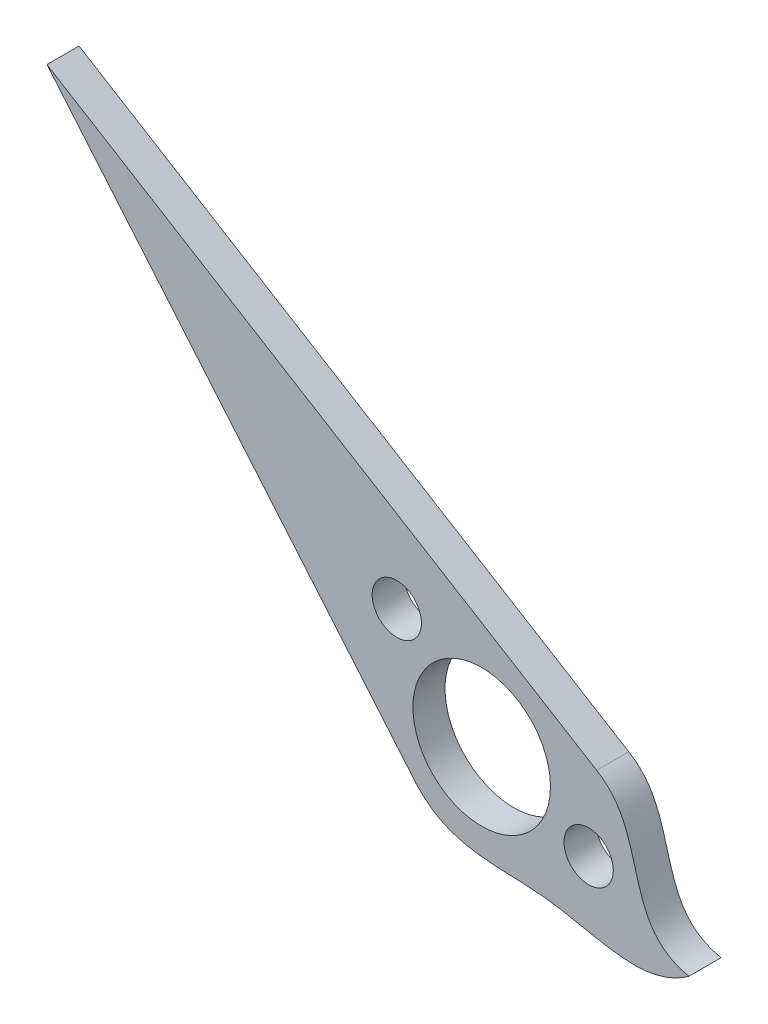
SolidWorks part; units mm, degrees
material "Titanium Ti-5Al-2.5Sn"
ref_plane "Front Plane" through (0, 0, 0) normal (0, 0, 1) x (1, 0, 0)
ref_plane "Top Plane" through (0, 0, 0) normal (0, 1, 0) x (1, 0, 0)
ref_plane "Right Plane" through (0, 0, 0) normal (1, 0, 0) x (0, 0, -1)
sketch "Sketch1" plane through (0, 0, 0) normal (0, 0, 1) x (1, 0, 0)
  line L0 (-5.6865, -5.6666) -> (-37.9242, 32.5846)
  line L1 (-37.9242, 32.5846) -> (10.0269, 3.2434)
  circle A1 centre (0, 0) radius 6
  circle A4 centre (-7.4069, 6.7184) radius 2.15
  circle A5 centre (9.3292, -3.6008) radius 2.15
  spline S0 degree 3 poles (10.0269, 3.2434) (14.6942, 0.5102) (12.1069, -7.0713) (18.0793, -8.2869) knots 0 0 0 0 1 1 1 1
  spline S1 degree 3 poles (-5.6865, -5.6666) (-2.6514, -9.0569) (6.1304, -7.2473) (14.1215, -11.1863) (18.0793, -8.2869) knots 0 0 0 0 0.488641 1 1 1 1
  point P1 (-30.9284, 30.63)
  point P8 (9.9514, -3.0464)
  point P11 (-7.0145, 6.3624)
  point P13 (-21.1241, 20.7713)
  point P14 (-5.934, -5.8738)
  point P15 (0, -9.3758)
  point P19 (0, 0)
  point P23 (9.1162, -2.673)
  point P24 (23.426, 0.6536)
  point P25 (0, 0)
  point P26 (0, 0)
  point P27 (13.4297, -0.5179)
  point P28 (18.0793, -8.2869)
  point P29 (13.4297, -9.8172)
  point P30 (12.2814, 1.1983)
  point P31 (12.3571, 1.2615)
  point P32 (0, 0)
  point P33 (12.2734, 1.1569)
  point P34 (5.7421, -8.661)
  point P35 (-2.2755, -7.8446)
  point P36 (14.837, -6.1832)
  point P37 (13.2404, -1.0742)
  point P38 (9.3292, -3.6008)
  point P39 (12.7843, -0.466)
  dimension "D1" = 12
  dimension "D2" = 50
  dimension "D3" = 10
  dimension "D5" = 8
  dimension "D4" = 10
  dimension "D6" = 8
extrude "Boss-Extrude3" add sketch "Sketch1" along normal blind 2.8 contours L0 region at (-21.2682, 13.9117, 0)
